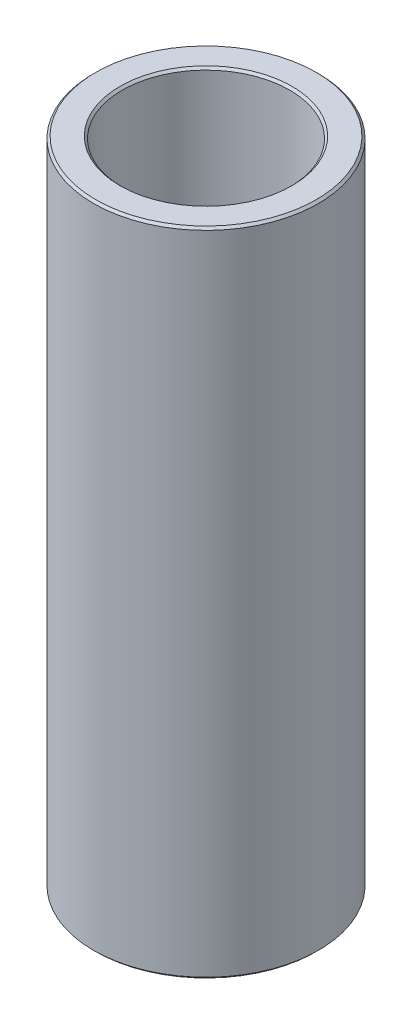
SolidWorks part; units mm, degrees
ref_plane "Front Plane" through (0, 0, 0) normal (0, 0, 1) x (1, 0, 0)
ref_plane "Top Plane" through (0, 0, 0) normal (0, 1, 0) x (1, 0, 0)
ref_plane "Right Plane" through (0, 0, 0) normal (1, 0, 0) x (0, 0, -1)
sketch "Sketch1" plane through (0, 0, 0) normal (0, 1, 0) x (1, 0, 0)
  circle A0 centre (0, 0) radius 42.5
  dimension "SLEEVE_OD" = 85
extrude "Boss-Extrude1" add sketch "Sketch1" along normal blind 246.0526
sketch "Sketch2" plane through (0, 0, 0) normal (0, 1, 0) x (1, 0, 0)
  circle A0 centre (0, 0) radius 31.6828
  dimension "BORE_D" = 63.3657
extrude "Cut-Extrude1" cut sketch "Sketch2" along normal through all
chamfer "Chamfer1" distance 0.8325 angle 45 4 edges at (0, 246.0526, 31.6828) (0, 0, 31.6828) (0, 0, 42.5) (0, 246.0526, 42.5)
